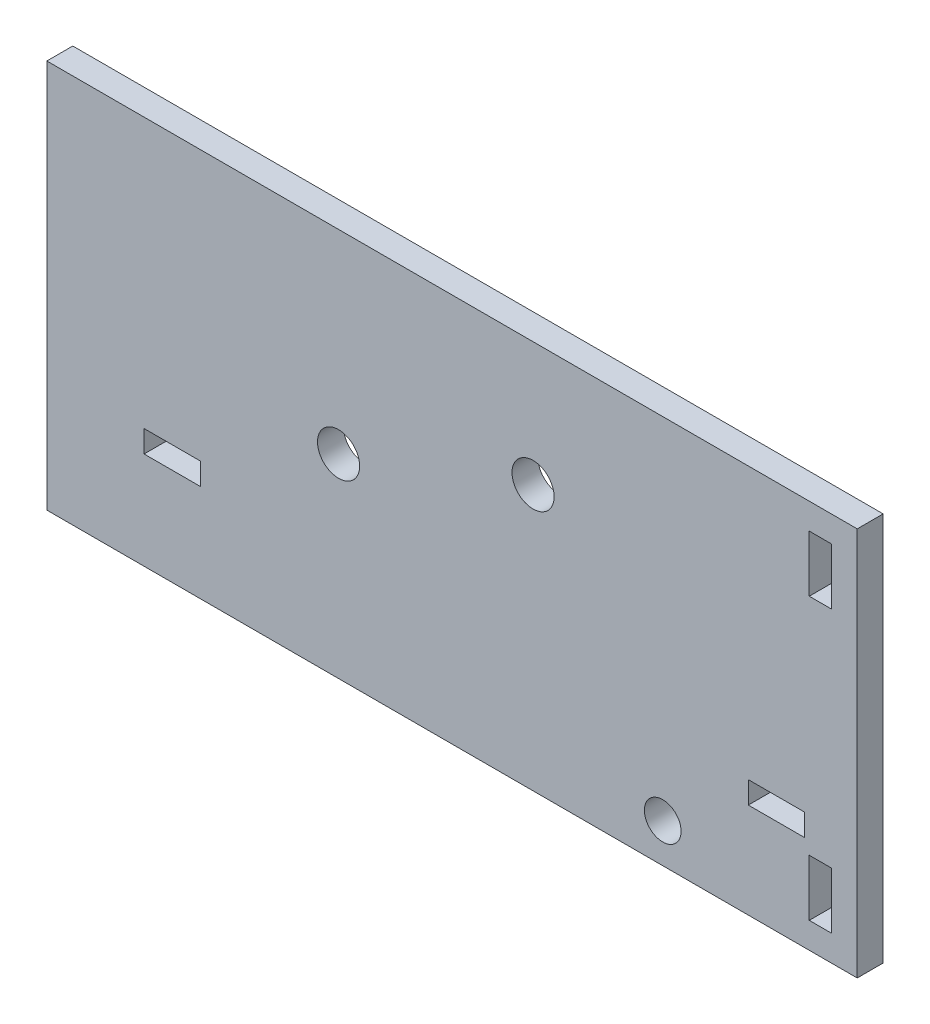
SolidWorks part; units mm, degrees
ref_plane "Front Plane" through (0, 0, 0) normal (0, 0, 1) x (1, 0, 0)
ref_plane "Top Plane" through (0, 0, 0) normal (0, 1, 0) x (1, 0, 0)
ref_plane "Right Plane" through (0, 0, 0) normal (1, 0, 0) x (0, 0, -1)
sketch "Sketch1" plane through (0, 0, 0) normal (0, 0, 1) x (1, 0, 0)
  line L1 (-79, -18.3961) -> (42, -18.3961)
  line L2 (-79, -18.3961) -> (-79, 41.6039)
  line L3 (-79, 41.6039) -> (42, 41.6039)
  line L4 (42, -18.3961) -> (42, 41.6039)
  line L5 (-64, 0.0039) -> (-55.3, 0.0039)
  line L6 (-64, 0.0039) -> (-64, -3.3961)
  line L7 (-64, -3.3961) -> (-55.3, -3.3961)
  line L8 (-55.3, 0.0039) -> (-55.3, -3.3961)
  line L9 (29.2, -0.2961) -> (37.9, -0.2961)
  line L10 (29.2, -0.2961) -> (29.2, -3.6961)
  line L11 (29.2, -3.6961) -> (37.9, -3.6961)
  line L12 (37.9, -0.2961) -> (37.9, -3.6961)
  circle A2 centre (-34, 11.6039) radius 3.25
  circle A3 centre (-4, 22.5) radius 3.25
  circle A4 centre (16, -12.3961) radius 2.83
  point P1 (0, 0)
  point P6 (-79, 11.6039)
  point P22 (-55.3, -1.6961)
  dimension "D3" = 0
  dimension "D4" = 121
  dimension "D5" = 45
  dimension "D6" = 8.7
  dimension "D7" = 30
  dimension "D10" = 6.5
  dimension "D12" = 95
  dimension "D13" = 6
  dimension "D14" = 5.66
  dimension "D15" = 46
  dimension "D2" = 60
  dimension "D8" = 3.4
  dimension "D9" = 15
  dimension "D11" = 15
  dimension "D16" = 84.5
  dimension "D17" = 22.5
extrude "Boss-Extrude1" add sketch "Sketch1" along normal blind 4
sketch "Sketch2" plane through (0, 0, 0) normal (0, 0, 1) x (1, 0, 0)
  line L0 (42, 41.6039) -> (46, 41.6039)
  line L1 (46, 41.6039) -> (46, -18.3961)
  line L2 (46, -18.3961) -> (42, -18.3961)
  line L13 (-79, -18.3961) -> (42, -18.3961) construction
  line L14 (42, -18.3961) -> (42, 41.6039)
  dimension "D1" = 4
extrude "Boss-Extrude2" add sketch "Sketch2" along normal blind 4
sketch "Sketch3" plane through (0, 0, 0) normal (0, 0, 1) x (1, 0, 0)
  line L0 (46, -18.3961) -> (46, 41.6039) construction
  line L1 (38.6, 37.6039) -> (42, 37.6039)
  line L2 (38.6, 37.6039) -> (38.6, 28.9039)
  line L3 (38.6, 28.9039) -> (42, 28.9039)
  line L4 (42, 37.6039) -> (42, 28.9039)
  line L5 (38.6, -5.6961) -> (42, -5.6961)
  line L6 (38.6, -5.6961) -> (38.6, -14.3961)
  line L7 (38.6, -14.3961) -> (42, -14.3961)
  line L8 (42, -5.6961) -> (42, -14.3961)
  line L9 (46, 41.6039) -> (-79, 41.6039) construction
  line L10 (-79, -18.3961) -> (46, -18.3961) construction
  dimension "D1" = 4
  dimension "D2" = 3.4
  dimension "D3" = 8.7
  dimension "D4" = 4
  dimension "D5" = 4
extrude "Cut-Extrude2" cut sketch "Sketch3" along normal through all both
equation "\"padding\"=4"
equation "\"hole_width\"=3.4"
equation "\"hole_height\"=8.7"
equation "\"D1@Sketch3\"=\"padding\""
equation "\"D2@Sketch3\"=\"hole_width\""
equation "\"D3@Sketch3\"=\"hole_height\""
equation "\"D4@Sketch3\"=\"padding\""
equation "\"D5@Sketch3\"=\"padding\""
